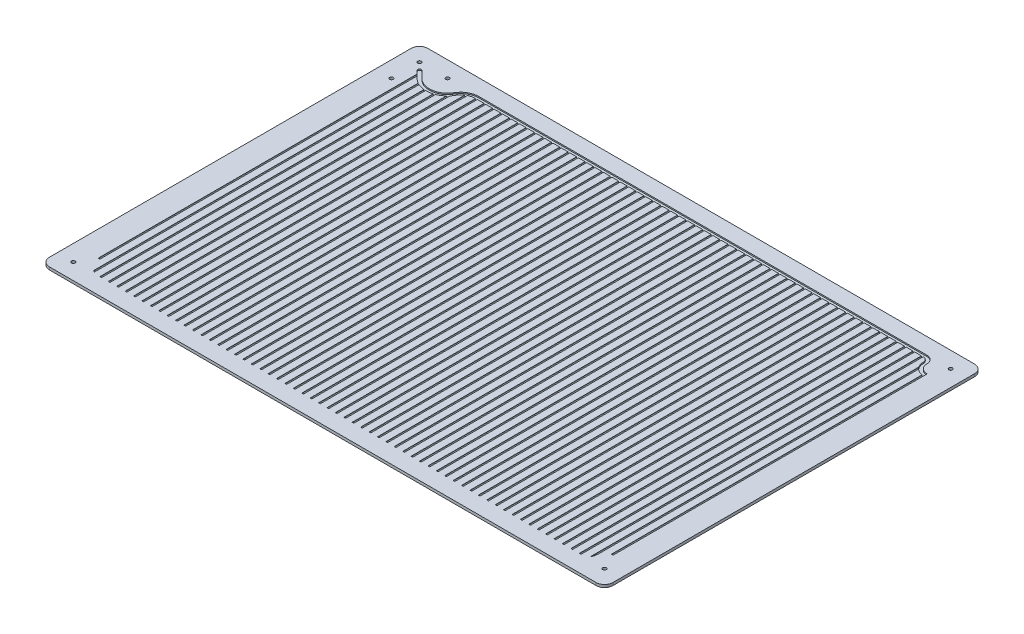
SolidWorks part; units mm, degrees
material "Alumina"
ref_plane "Front Plane" through (0, 0, 0) normal (0, 0, 1) x (1, 0, 0)
ref_plane "Top Plane" through (0, 0, 0) normal (0, 1, 0) x (1, 0, 0)
ref_plane "Right Plane" through (0, 0, 0) normal (1, 0, 0) x (0, 0, -1)
sketch "Sketch1" plane through (0, 0, 0) normal (0, 1, 0) x (1, 0, 0)
  line L1 (-300, -225) -> (300, -225)
  line L2 (-300, -225) -> (-300, 225) construction
  line L3 (-300, 225) -> (300, 225)
  line L4 (300, -225) -> (300, 225)
  line L5 (-300, -225) -> (300, 225) construction
  line L6 (-300, 225) -> (300, -225) construction
  line L7 (-370, -225) -> (-300, -225)
  line L8 (-370, -225) -> (-370, 225)
  line L9 (-370, 225) -> (-300, 225)
  line L10 (-300, -225) -> (-300, 225)
  line L11 (-370, -225) -> (-300, 225) construction
  line L12 (-370, 225) -> (-300, -225) construction
  point P0 (0, 0)
  point P6 (-335, 0)
  dimension "D1" = 450
  dimension "D2" = 600
  dimension "D3" = 70
extrude "Boss-Extrude1" add sketch "Sketch1" along normal blind 3.2 contours L7 L10 L9 L8 | L10 L1 L4 L3 region at (0, 0, 0) region at (-335, 0, 0)
sketch "Sketch2" plane through (0, 3.2, 0) normal (0, 1, 0) x (1, 0, 0)
  line L0 (-300, -225) -> (300, -225) construction
  line L1 (300, -225) -> (300, 225) construction
  line L2 (-300, 225) -> (300, 225) construction
  line L3 (-370, 225) -> (-300, 225) construction
  line L4 (-370, -225) -> (-370, 225) construction
  line L6 (-300, -225) -> (300, -225) construction
  line L7 (300, -225) -> (300, 225) construction
  line L8 (-300, 225) -> (300, 225) construction
  line L9 (-370, 225) -> (-300, 225) construction
  line L10 (-370, -225) -> (-370, 225) construction
  line L12 (-370, 225) -> (-350.8076, 205.8076) construction
  line L13 (-350.8076, 205.8076) -> (280.8076, 205.8076) construction
  line L14 (-350.8076, 205.8076) -> (-350.8076, -205.8076) construction
  line L15 (-350.8076, -205.8076) -> (280.8076, -205.8076) construction
  line L16 (280.8076, 205.8076) -> (280.8076, -205.8076) construction
  line L17 (280.8076, 205.8076) -> (300, 225) construction
  line L18 (280.8076, -205.8076) -> (300, -225) construction
  line L19 (-340.8076, 215.8076) -> (35014.5314, 35571.1467) construction
  line L20 (-35, 205.8076) -> (-35, -49794.1924) construction
  line L21 (0, 0) -> (50000, 0) construction
  line L22 (-331.6152, 186.6152) -> (35023.723, -35168.7247) construction
  line L23 (-270, 225) -> (-370, 125) construction
  circle A0 centre (-350.8076, 205.8076) radius 3 construction
  arc A1 (-370, 215) -> (-360, 225) centre (-360, 215) cw construction
  arc A2 (-341.6152, 186.6152) -> (-331.6152, 196.6152) centre (-341.6152, 196.6152) ccw construction
  arc A3 (271.6152, 186.6152) -> (261.6152, 196.6152) centre (271.6152, 196.6152) cw construction
  arc A4 (271.6152, -186.6152) -> (261.6152, -196.6152) centre (271.6152, -196.6152) ccw construction
  arc A5 (-341.6152, 186.6152) -> (-350.8076, 177.4228) centre (-341.6152, 177.4228) ccw construction
  arc A6 (-331.6152, 196.6152) -> (-322.4228, 205.8076) centre (-322.4228, 196.6152) cw construction
  arc A7 (271.6152, 186.6152) -> (280.8076, 177.4228) centre (271.6152, 177.4228) cw construction
  arc A8 (261.6152, 196.6152) -> (252.4228, 205.8076) centre (252.4228, 196.6152) ccw construction
  arc A9 (261.6152, -196.6152) -> (252.4228, -205.8076) centre (252.4228, -196.6152) cw construction
  arc A10 (271.6152, -186.6152) -> (280.8076, -177.4228) centre (271.6152, -177.4228) ccw construction
  circle A11 centre (-350.8076, 172.4767) radius 3 construction
  circle A13 centre (-317.4767, 205.8076) radius 3 construction
  arc A15 (-331.6152, -196.6152) -> (-322.4228, -205.8076) centre (-322.4228, -196.6152) ccw construction
  arc A16 (-341.6152, -186.6152) -> (-331.6152, -196.6152) centre (-341.6152, -196.6152) cw construction
  arc A17 (-341.6152, -186.6152) -> (-350.8076, -177.4228) centre (-341.6152, -177.4228) cw construction
  point P10 (-352.9289, 207.9289)
  point P16 (-367.0711, 222.0711)
  point P27 (-35, 205.8076)
  point P39 (-334.5442, 189.5442)
  point P53 (-350.8076, 175.4767)
  point P56 (-350.8076, 202.8076)
  dimension "D2" = 6
  dimension "D3" = 10
  dimension "D1" = 45
  dimension "D4" = 20
  dimension "D5" = 45
  dimension "D6" = 100
  dimension "D7" = 20
  dimension "D8" = 27.3309
sketch "Sketch6" plane through (0, 3.2, 0) normal (0, 1, 0) x (1, 0, 0)
  line L0 (280.8076, 177.4228) -> (280.8076, -177.4228) construction
  line L1 (-280, 205.8076) -> (252.4228, 205.8076) construction
  line L2 (-350.8076, 205.8076) -> (280.8076, 205.8076) construction
  line L5 (-350.8076, -205.8076) -> (280.8076, -205.8076) construction
  line L6 (-280, -205.8076) -> (252.4228, -205.8076) construction
  line L7 (-141752.968, 141607.9749) -> (176445.0758, -176590.0843) construction
  line L8 (-341.0607, 198.8891) -> (-332.7279, 190.5564)
  line L9 (-343.8891, 196.0607) -> (-341.0607, 198.8891) construction
  line L10 (-350.8076, 172.4767) -> (-317.4767, 205.8076) construction
  line L11 (-350.8076, 205.8076) -> (-334.1421, 189.1421) construction
  line L12 (-343.8891, 196.0607) -> (-335.5564, 187.7279)
  line L13 (-283.4499, 201.8076) -> (-67.3575, 201.8076) construction
  line L14 (-280, 205.8076) -> (-280, 201.8076)
  line L16 (-280, 224.1399) -> (-280, -49775.8601) construction
  line L17 (-300, -225) -> (-300, 225) construction
  line L18 (-300, -225) -> (-300, 225) construction
  arc A0 (271.6152, -186.6152) -> (280.8076, -177.4228) centre (271.6152, -177.4228) ccw construction
  arc A1 (271.6152, -186.6152) -> (261.6152, -196.6152) centre (271.6152, -196.6152) ccw construction
  arc A2 (252.4228, -205.8076) -> (261.6152, -196.6152) centre (252.4228, -196.6152) ccw construction
  arc A3 (280.8076, 177.4228) -> (271.6152, 186.6152) centre (271.6152, 177.4228) ccw construction
  arc A4 (261.6152, 196.6152) -> (271.6152, 186.6152) centre (271.6152, 196.6152) ccw construction
  arc A5 (261.6152, 196.6152) -> (252.4228, 205.8076) centre (252.4228, 196.6152) ccw construction
  arc A6 (271.6152, -186.6152) -> (280.8076, -177.4228) centre (271.6152, -177.4228) ccw construction
  arc A7 (271.6152, -186.6152) -> (261.6152, -196.6152) centre (271.6152, -196.6152) ccw construction
  arc A8 (252.4228, -205.8076) -> (261.6152, -196.6152) centre (252.4228, -196.6152) ccw construction
  arc A9 (280.8076, 177.4228) -> (271.6152, 186.6152) centre (271.6152, 177.4228) ccw construction
  arc A10 (261.6152, 196.6152) -> (271.6152, 186.6152) centre (271.6152, 196.6152) ccw construction
  arc A11 (261.6152, 196.6152) -> (252.4228, 205.8076) centre (252.4228, 196.6152) ccw construction
  arc A12 (-298.8275, 194.972) -> (-332.7279, 190.5564) centre (-317.4767, 205.8076) cw
  arc A13 (-335.5564, 187.7279) -> (-295.3689, 192.9625) centre (-317.4767, 205.8076) ccw
  arc A14 (-341.0607, 198.8891) -> (-343.8891, 196.0607) centre (-342.4749, 197.4749) ccw
  arc A15 (-298.8275, 194.972) -> (-280, 205.8076) centre (-280, 184.0329) cw
  arc A16 (-295.3689, 192.9625) -> (-280, 201.8076) centre (-280, 184.0329) cw
  point P31 (-342.4749, 197.4749)
  dimension "D1" = 4
  dimension "D2" = 20
extrude "Cut-Extrude1" cut sketch "Sketch6" against normal blind 1.5
hole_wizard "Tap Drill for M5x0.8 Tap2" positions "3DSketch4" profile "Sketch10" hole size "M5x0.8" standard "ANSI Metric" end condition through all
sketch3d "3DSketch4"
  point P0 (-350.8076, 3.2, 205.8076)
  point P3 (-350.8076, 3.2, -205.8076)
  point P6 (-317.4767, 3.2, -205.8076)
  point P9 (-350.8076, 3.2, -172.4767)
  point P12 (280.8076, 3.2, -205.8076)
  point P15 (280.8076, 3.2, 205.8076)
sketch "Sketch10" plane through (-350.8076, 3.2, 205.8076) normal (1, 0, 0) x (0, 0, 1)
  line L0 (0, 0) -> (0, 3.2)
  line L1 (0, 3.2) -> (2.1, 3.2)
  line L2 (2.1, 3.2) -> (2.1, 0)
  line L5 (2.1, 0) -> (0, 0)
  line L11 (0, -6.35) -> (0, 107.95) construction
  dimension "Thru Hole Dia." = 4.2
  dimension "Thru Hole Depth" = 3.2
sketch "Sketch11" plane through (0, 0, 225) normal (0, 0, 1) x (1, 0, 0)
  line L0 (-280, 3.2) -> (-298.8275, 3.2) construction
  line L1 (-280, 3.2) -> (-298.8275, 3.2) construction
  line L3 (-280, 3.2) -> (-280, 2.7)
  line L4 (-280, 3.2) -> (-278, 3.2)
  line L5 (-141762.1638, 3.2) -> (176435.8877, 3.2) construction
  line L6 (-278, 3.2) -> (-278, 2.7)
  line L7 (-270, 3.2) -> (-270, 2.7)
  line L8 (-270, 3.2) -> (-268, 3.2)
  line L9 (-268, 3.2) -> (-268, 2.7)
  line L10 (-260, 3.2) -> (-260, 2.7)
  line L11 (-260, 3.2) -> (-258, 3.2)
  line L12 (-258, 3.2) -> (-258, 2.7)
  line L13 (-250, 3.2) -> (-250, 2.7)
  line L14 (-250, 3.2) -> (-248, 3.2)
  line L15 (-248, 3.2) -> (-248, 2.7)
  line L16 (-240, 3.2) -> (-240, 2.7)
  line L17 (-240, 3.2) -> (-238, 3.2)
  line L18 (-238, 3.2) -> (-238, 2.7)
  line L19 (-230, 3.2) -> (-230, 2.7)
  line L20 (-230, 3.2) -> (-228, 3.2)
  line L21 (-228, 3.2) -> (-228, 2.7)
  line L22 (-220, 3.2) -> (-220, 2.7)
  line L23 (-220, 3.2) -> (-218, 3.2)
  line L24 (-218, 3.2) -> (-218, 2.7)
  line L25 (-210, 3.2) -> (-210, 2.7)
  line L26 (-210, 3.2) -> (-208, 3.2)
  line L27 (-208, 3.2) -> (-208, 2.7)
  line L28 (-200, 3.2) -> (-200, 2.7)
  line L29 (-200, 3.2) -> (-198, 3.2)
  line L30 (-198, 3.2) -> (-198, 2.7)
  line L31 (-190, 3.2) -> (-190, 2.7)
  line L32 (-190, 3.2) -> (-188, 3.2)
  line L33 (-188, 3.2) -> (-188, 2.7)
  line L34 (-180, 3.2) -> (-180, 2.7)
  line L35 (-180, 3.2) -> (-178, 3.2)
  line L36 (-178, 3.2) -> (-178, 2.7)
  line L37 (-170, 3.2) -> (-170, 2.7)
  line L38 (-170, 3.2) -> (-168, 3.2)
  line L39 (-168, 3.2) -> (-168, 2.7)
  line L40 (-160, 3.2) -> (-160, 2.7)
  line L41 (-160, 3.2) -> (-158, 3.2)
  line L42 (-158, 3.2) -> (-158, 2.7)
  line L43 (-150, 3.2) -> (-150, 2.7)
  line L44 (-150, 3.2) -> (-148, 3.2)
  line L45 (-148, 3.2) -> (-148, 2.7)
  line L46 (-140, 3.2) -> (-140, 2.7)
  line L47 (-140, 3.2) -> (-138, 3.2)
  line L48 (-138, 3.2) -> (-138, 2.7)
  line L49 (-130, 3.2) -> (-130, 2.7)
  line L50 (-130, 3.2) -> (-128, 3.2)
  line L51 (-128, 3.2) -> (-128, 2.7)
  line L52 (-120, 3.2) -> (-120, 2.7)
  line L53 (-120, 3.2) -> (-118, 3.2)
  line L54 (-118, 3.2) -> (-118, 2.7)
  line L55 (-110, 3.2) -> (-110, 2.7)
  line L56 (-110, 3.2) -> (-108, 3.2)
  line L57 (-108, 3.2) -> (-108, 2.7)
  line L58 (-100, 3.2) -> (-100, 2.7)
  line L59 (-100, 3.2) -> (-98, 3.2)
  line L60 (-98, 3.2) -> (-98, 2.7)
  line L61 (-90, 3.2) -> (-90, 2.7)
  line L62 (-90, 3.2) -> (-88, 3.2)
  line L63 (-88, 3.2) -> (-88, 2.7)
  line L64 (-80, 3.2) -> (-80, 2.7)
  line L65 (-80, 3.2) -> (-78, 3.2)
  line L66 (-78, 3.2) -> (-78, 2.7)
  line L67 (-70, 3.2) -> (-70, 2.7)
  line L68 (-70, 3.2) -> (-68, 3.2)
  line L69 (-68, 3.2) -> (-68, 2.7)
  line L70 (-60, 3.2) -> (-60, 2.7)
  line L71 (-60, 3.2) -> (-58, 3.2)
  line L72 (-58, 3.2) -> (-58, 2.7)
  line L73 (-50, 3.2) -> (-50, 2.7)
  line L74 (-50, 3.2) -> (-48, 3.2)
  line L75 (-48, 3.2) -> (-48, 2.7)
  line L76 (-40, 3.2) -> (-40, 2.7)
  line L77 (-40, 3.2) -> (-38, 3.2)
  line L78 (-38, 3.2) -> (-38, 2.7)
  line L79 (-30, 3.2) -> (-30, 2.7)
  line L80 (-30, 3.2) -> (-28, 3.2)
  line L81 (-28, 3.2) -> (-28, 2.7)
  line L82 (-20, 3.2) -> (-20, 2.7)
  line L83 (-20, 3.2) -> (-18, 3.2)
  line L84 (-18, 3.2) -> (-18, 2.7)
  line L85 (-10, 3.2) -> (-10, 2.7)
  line L86 (-10, 3.2) -> (-8, 3.2)
  line L87 (-8, 3.2) -> (-8, 2.7)
  line L88 (0, 3.2) -> (0, 2.7)
  line L89 (0, 3.2) -> (2, 3.2)
  line L90 (2, 3.2) -> (2, 2.7)
  line L91 (10, 3.2) -> (10, 2.7)
  line L92 (10, 3.2) -> (12, 3.2)
  line L93 (12, 3.2) -> (12, 2.7)
  line L94 (20, 3.2) -> (20, 2.7)
  line L95 (20, 3.2) -> (22, 3.2)
  line L96 (22, 3.2) -> (22, 2.7)
  line L97 (30, 3.2) -> (30, 2.7)
  line L98 (30, 3.2) -> (32, 3.2)
  line L99 (32, 3.2) -> (32, 2.7)
  line L100 (40, 3.2) -> (40, 2.7)
  line L101 (40, 3.2) -> (42, 3.2)
  line L102 (42, 3.2) -> (42, 2.7)
  line L103 (50, 3.2) -> (50, 2.7)
  line L104 (50, 3.2) -> (52, 3.2)
  line L105 (52, 3.2) -> (52, 2.7)
  line L106 (60, 3.2) -> (60, 2.7)
  line L107 (60, 3.2) -> (62, 3.2)
  line L108 (62, 3.2) -> (62, 2.7)
  line L109 (70, 3.2) -> (70, 2.7)
  line L110 (70, 3.2) -> (72, 3.2)
  line L111 (72, 3.2) -> (72, 2.7)
  line L112 (80, 3.2) -> (80, 2.7)
  line L113 (80, 3.2) -> (82, 3.2)
  line L114 (82, 3.2) -> (82, 2.7)
  line L115 (90, 3.2) -> (90, 2.7)
  line L116 (90, 3.2) -> (92, 3.2)
  line L117 (92, 3.2) -> (92, 2.7)
  line L118 (100, 3.2) -> (100, 2.7)
  line L119 (100, 3.2) -> (102, 3.2)
  line L120 (102, 3.2) -> (102, 2.7)
  line L121 (110, 3.2) -> (110, 2.7)
  line L122 (110, 3.2) -> (112, 3.2)
  line L123 (112, 3.2) -> (112, 2.7)
  line L124 (120, 3.2) -> (120, 2.7)
  line L125 (120, 3.2) -> (122, 3.2)
  line L126 (122, 3.2) -> (122, 2.7)
  line L127 (130, 3.2) -> (130, 2.7)
  line L128 (130, 3.2) -> (132, 3.2)
  line L129 (132, 3.2) -> (132, 2.7)
  line L130 (140, 3.2) -> (140, 2.7)
  line L131 (140, 3.2) -> (142, 3.2)
  line L132 (142, 3.2) -> (142, 2.7)
  line L133 (150, 3.2) -> (150, 2.7)
  line L134 (150, 3.2) -> (152, 3.2)
  line L135 (152, 3.2) -> (152, 2.7)
  line L136 (160, 3.2) -> (160, 2.7)
  line L137 (160, 3.2) -> (162, 3.2)
  line L138 (162, 3.2) -> (162, 2.7)
  line L139 (170, 3.2) -> (170, 2.7)
  line L140 (170, 3.2) -> (172, 3.2)
  line L141 (172, 3.2) -> (172, 2.7)
  line L142 (180, 3.2) -> (180, 2.7)
  line L143 (180, 3.2) -> (182, 3.2)
  line L144 (182, 3.2) -> (182, 2.7)
  line L145 (190, 3.2) -> (190, 2.7)
  line L146 (190, 3.2) -> (192, 3.2)
  line L147 (192, 3.2) -> (192, 2.7)
  line L148 (200, 3.2) -> (200, 2.7)
  line L149 (200, 3.2) -> (202, 3.2)
  line L150 (202, 3.2) -> (202, 2.7)
  line L151 (210, 3.2) -> (210, 2.7)
  line L152 (210, 3.2) -> (212, 3.2)
  line L153 (212, 3.2) -> (212, 2.7)
  line L154 (220, 3.2) -> (220, 2.7)
  line L155 (220, 3.2) -> (222, 3.2)
  line L156 (222, 3.2) -> (222, 2.7)
  line L157 (230, 3.2) -> (230, 2.7)
  line L158 (230, 3.2) -> (232, 3.2)
  line L159 (232, 3.2) -> (232, 2.7)
  line L160 (240, 3.2) -> (240, 2.7)
  line L161 (240, 3.2) -> (242, 3.2)
  line L162 (242, 3.2) -> (242, 2.7)
  line L163 (250, 3.2) -> (250, 2.7)
  line L164 (250, 3.2) -> (252, 3.2)
  line L165 (252, 3.2) -> (252, 2.7)
  line L166 (260, 3.2) -> (260, 2.7)
  line L167 (260, 3.2) -> (262, 3.2)
  line L168 (262, 3.2) -> (262, 2.7)
  line L169 (270, 3.2) -> (270, 2.7)
  line L170 (270, 3.2) -> (272, 3.2)
  line L171 (272, 3.2) -> (272, 2.7)
  line L172 (-280, 3.2) -> (-270, 3.2) construction
  line L173 (-300, 3.2) -> (300, 3.2) construction
  line L174 (-290, 3.2) -> (-290, 2.7)
  line L175 (-288, 3.2) -> (-288, 2.7)
  line L176 (-290, 3.2) -> (-288, 3.2)
  line L177 (-300, 3.2) -> (-300, 2.7)
  line L178 (-298, 3.2) -> (-298, 2.7)
  line L179 (-300, 3.2) -> (-298, 3.2)
  line L180 (-310, 3.2) -> (-310, 2.7)
  line L181 (-308, 3.2) -> (-308, 2.7)
  line L182 (-310, 3.2) -> (-308, 3.2)
  line L183 (-320, 3.2) -> (-320, 2.7)
  line L184 (-318, 3.2) -> (-318, 2.7)
  line L185 (-320, 3.2) -> (-318, 3.2)
  line L186 (-330, 3.2) -> (-330, 2.7)
  line L187 (-328, 3.2) -> (-328, 2.7)
  line L188 (-330, 3.2) -> (-328, 3.2)
  line L189 (-340, 3.2) -> (-340, 2.7)
  line L190 (-338, 3.2) -> (-338, 2.7)
  line L191 (-340, 3.2) -> (-338, 3.2)
  line L192 (-280, 2.7) -> (-290, 2.7) construction
  arc A0 (-280, 2.7) -> (-278, 2.7) centre (-279, 2.7) ccw
  arc A1 (-270, 2.7) -> (-268, 2.7) centre (-269, 2.7) ccw
  arc A2 (-260, 2.7) -> (-258, 2.7) centre (-259, 2.7) ccw
  arc A3 (-250, 2.7) -> (-248, 2.7) centre (-249, 2.7) ccw
  arc A4 (-240, 2.7) -> (-238, 2.7) centre (-239, 2.7) ccw
  arc A5 (-230, 2.7) -> (-228, 2.7) centre (-229, 2.7) ccw
  arc A6 (-220, 2.7) -> (-218, 2.7) centre (-219, 2.7) ccw
  arc A7 (-210, 2.7) -> (-208, 2.7) centre (-209, 2.7) ccw
  arc A8 (-200, 2.7) -> (-198, 2.7) centre (-199, 2.7) ccw
  arc A9 (-190, 2.7) -> (-188, 2.7) centre (-189, 2.7) ccw
  arc A10 (-180, 2.7) -> (-178, 2.7) centre (-179, 2.7) ccw
  arc A11 (-170, 2.7) -> (-168, 2.7) centre (-169, 2.7) ccw
  arc A12 (-160, 2.7) -> (-158, 2.7) centre (-159, 2.7) ccw
  arc A13 (-150, 2.7) -> (-148, 2.7) centre (-149, 2.7) ccw
  arc A14 (-140, 2.7) -> (-138, 2.7) centre (-139, 2.7) ccw
  arc A15 (-130, 2.7) -> (-128, 2.7) centre (-129, 2.7) ccw
  arc A16 (-120, 2.7) -> (-118, 2.7) centre (-119, 2.7) ccw
  arc A17 (-110, 2.7) -> (-108, 2.7) centre (-109, 2.7) ccw
  arc A18 (-100, 2.7) -> (-98, 2.7) centre (-99, 2.7) ccw
  arc A19 (-90, 2.7) -> (-88, 2.7) centre (-89, 2.7) ccw
  arc A20 (-80, 2.7) -> (-78, 2.7) centre (-79, 2.7) ccw
  arc A21 (-70, 2.7) -> (-68, 2.7) centre (-69, 2.7) ccw
  arc A22 (-60, 2.7) -> (-58, 2.7) centre (-59, 2.7) ccw
  arc A23 (-50, 2.7) -> (-48, 2.7) centre (-49, 2.7) ccw
  arc A24 (-40, 2.7) -> (-38, 2.7) centre (-39, 2.7) ccw
  arc A25 (-30, 2.7) -> (-28, 2.7) centre (-29, 2.7) ccw
  arc A26 (-20, 2.7) -> (-18, 2.7) centre (-19, 2.7) ccw
  arc A27 (-10, 2.7) -> (-8, 2.7) centre (-9, 2.7) ccw
  arc A28 (0, 2.7) -> (2, 2.7) centre (1, 2.7) ccw
  arc A29 (10, 2.7) -> (12, 2.7) centre (11, 2.7) ccw
  arc A30 (20, 2.7) -> (22, 2.7) centre (21, 2.7) ccw
  arc A31 (30, 2.7) -> (32, 2.7) centre (31, 2.7) ccw
  arc A32 (40, 2.7) -> (42, 2.7) centre (41, 2.7) ccw
  arc A33 (50, 2.7) -> (52, 2.7) centre (51, 2.7) ccw
  arc A34 (60, 2.7) -> (62, 2.7) centre (61, 2.7) ccw
  arc A35 (70, 2.7) -> (72, 2.7) centre (71, 2.7) ccw
  arc A36 (80, 2.7) -> (82, 2.7) centre (81, 2.7) ccw
  arc A37 (90, 2.7) -> (92, 2.7) centre (91, 2.7) ccw
  arc A38 (100, 2.7) -> (102, 2.7) centre (101, 2.7) ccw
  arc A39 (110, 2.7) -> (112, 2.7) centre (111, 2.7) ccw
  arc A40 (120, 2.7) -> (122, 2.7) centre (121, 2.7) ccw
  arc A41 (130, 2.7) -> (132, 2.7) centre (131, 2.7) ccw
  arc A42 (140, 2.7) -> (142, 2.7) centre (141, 2.7) ccw
  arc A43 (150, 2.7) -> (152, 2.7) centre (151, 2.7) ccw
  arc A44 (160, 2.7) -> (162, 2.7) centre (161, 2.7) ccw
  arc A45 (170, 2.7) -> (172, 2.7) centre (171, 2.7) ccw
  arc A46 (180, 2.7) -> (182, 2.7) centre (181, 2.7) ccw
  arc A47 (190, 2.7) -> (192, 2.7) centre (191, 2.7) ccw
  arc A48 (200, 2.7) -> (202, 2.7) centre (201, 2.7) ccw
  arc A49 (210, 2.7) -> (212, 2.7) centre (211, 2.7) ccw
  arc A50 (220, 2.7) -> (222, 2.7) centre (221, 2.7) ccw
  arc A51 (230, 2.7) -> (232, 2.7) centre (231, 2.7) ccw
  arc A52 (240, 2.7) -> (242, 2.7) centre (241, 2.7) ccw
  arc A53 (250, 2.7) -> (252, 2.7) centre (251, 2.7) ccw
  arc A54 (260, 2.7) -> (262, 2.7) centre (261, 2.7) ccw
  arc A55 (270, 2.7) -> (272, 2.7) centre (271, 2.7) ccw
  arc A56 (-290, 2.7) -> (-288, 2.7) centre (-289, 2.7) ccw
  arc A57 (-300, 2.7) -> (-298, 2.7) centre (-299, 2.7) ccw
  arc A58 (-310, 2.7) -> (-308, 2.7) centre (-309, 2.7) ccw
  arc A59 (-320, 2.7) -> (-318, 2.7) centre (-319, 2.7) ccw
  arc A60 (-330, 2.7) -> (-328, 2.7) centre (-329, 2.7) ccw
  arc A61 (-340, 2.7) -> (-338, 2.7) centre (-339, 2.7) ccw
  point P0 (-300, 3.2)
  dimension "D2" = 1
  dimension "D1" = 0.5
  dimension "D4" = 10
  dimension "D6" = 10
  dimension "D3" = 56
  dimension "D5" = 7
extrude "Cut-Extrude2" cut sketch "Sketch11" against normal offset from surface (410 mm away) 20 from offset 20 up to face at (-35, 1.6, -225) offset against normal yes
sketch "Sketch12" plane through (0, 3.2, 0) normal (0, 1, 0) x (1, 0, 0)
  line L0 (-280, 205.8076) -> (-315.3767, 205.8076)
  line L1 (-350.8076, 205.8076) -> (280.8076, 205.8076) construction
  line L2 (-350.8076, 205.8076) -> (-350.8076, -205.8076) construction
  line L3 (-350.8076, 202.8076) -> (-350.8076, 177.4228)
  line L4 (-350.8076, -177.4228) -> (-350.8076, -203.7076)
  line L5 (-332.7279, 190.5564) -> (-339, 196.8284)
  line L6 (-339, 196.8284) -> (-341.0607, 198.8891)
  line L7 (-343.8891, 196.0607) -> (-339, 191.1716)
  line L8 (-339, 191.1716) -> (-335.5564, 187.7279)
  line L9 (-280, 201.8076) -> (-280, 205.8076)
  line L10 (-332.7279, 190.5564) -> (-339, 196.8284)
  line L11 (-339, 196.8284) -> (-341.0607, 198.8891)
  line L12 (-343.8891, 196.0607) -> (-340, 192.1716)
  line L15 (-350.8076, -205.8076) -> (280.8076, -205.8076) construction
  line L16 (-348.7076, -205.8076) -> (-322.4228, -205.8076)
  line L17 (-35, -225) -> (-35, 49775) construction
  line L19 (-35, 200205.8076) -> (-35, -249794.1924) construction
  line L20 (0, 0) -> (-49761.8351, 0) construction
  line L22 (-200000, 0) -> (250000, 0) construction
  line L23 (278.7076, -205.8076) -> (252.4228, -205.8076)
  line L24 (280.8076, -177.4228) -> (280.8076, -203.7076)
  line L25 (280.8076, 177.4228) -> (280.8076, 203.7076)
  line L26 (278.7076, 205.8076) -> (252.4228, 205.8076)
  line L27 (-319.5767, 205.8076) -> (-347.8076, 205.8076)
  line L28 (-340, 192.1716) -> (-340, 186.7465)
  line L29 (-340, 192.1716) -> (-340, -205) construction
  arc A6 (-331.6152, -196.6152) -> (-322.4228, -205.8076) centre (-322.4228, -196.6152) ccw construction
  arc A7 (-331.6152, -196.6152) -> (-341.6152, -186.6152) centre (-341.6152, -196.6152) ccw construction
  arc A8 (-350.8076, -177.4228) -> (-341.6152, -186.6152) centre (-341.6152, -177.4228) ccw construction
  arc A9 (280.8076, -203.7076) -> (278.7076, -205.8076) centre (280.8076, -205.8076) ccw
  arc A10 (280.8076, -177.4228) -> (271.6152, -186.6152) centre (271.6152, -177.4228) cw
  arc A11 (261.6152, -196.6152) -> (271.6152, -186.6152) centre (271.6152, -196.6152) cw
  arc A12 (261.6152, -196.6152) -> (252.4228, -205.8076) centre (252.4228, -196.6152) cw
  arc A13 (261.6152, 196.6152) -> (252.4228, 205.8076) centre (252.4228, 196.6152) ccw
  arc A14 (261.6152, 196.6152) -> (271.6152, 186.6152) centre (271.6152, 196.6152) ccw
  arc A15 (-280, 205.8076) -> (-289, 203.8606) centre (-280, 184.0329) ccw
  arc A16 (-289, 203.8606) -> (-298.8275, 194.972) centre (-280, 184.0329) ccw
  arc A17 (-299, 194.6804) -> (-298.8275, 194.972) centre (-317.4767, 205.8076) ccw
  arc A18 (-309, 185.9746) -> (-299, 194.6804) centre (-317.4767, 205.8076) ccw
  arc A19 (-319, 184.2929) -> (-309, 185.9746) centre (-317.4767, 205.8076) ccw
  arc A20 (-329, 187.5754) -> (-319, 184.2929) centre (-317.4767, 205.8076) ccw
  arc A21 (-332.7279, 190.5564) -> (-329, 187.5754) centre (-317.4767, 205.8076) ccw
  arc A22 (-341.0607, 198.8891) -> (-343.8891, 196.0607) centre (-342.4749, 197.4749) ccw
  arc A23 (-335.5564, 187.7279) -> (-329, 182.983) centre (-317.4767, 205.8076) ccw
  arc A24 (-329, 182.983) -> (-319, 180.2845) centre (-317.4767, 205.8076) ccw
  arc A25 (-319, 180.2845) -> (-309, 181.6851) centre (-317.4767, 205.8076) ccw
  arc A26 (-309, 181.6851) -> (-299, 188.1338) centre (-317.4767, 205.8076) ccw
  arc A27 (-299, 188.1338) -> (-295.3689, 192.9625) centre (-317.4767, 205.8076) ccw
  arc A28 (-289, 199.3607) -> (-295.3689, 192.9625) centre (-280, 184.0329) ccw
  arc A29 (-280, 201.8076) -> (-289, 199.3607) centre (-280, 184.0329) ccw
  arc A30 (-280, 205.8076) -> (-289, 203.8606) centre (-280, 184.0329) ccw
  arc A31 (-289, 203.8606) -> (-298.8275, 194.972) centre (-280, 184.0329) ccw
  arc A32 (-299, 194.6804) -> (-298.8275, 194.972) centre (-317.4767, 205.8076) ccw
  arc A33 (-309, 185.9746) -> (-299, 194.6804) centre (-317.4767, 205.8076) ccw
  arc A34 (-319, 184.2929) -> (-309, 185.9746) centre (-317.4767, 205.8076) ccw
  arc A35 (-329, 187.5754) -> (-319, 184.2929) centre (-317.4767, 205.8076) ccw
  arc A36 (-332.7279, 190.5564) -> (-329, 187.5754) centre (-317.4767, 205.8076) ccw
  arc A37 (-341.0607, 198.8891) -> (-343.8891, 196.0607) centre (-342.4749, 197.4749) ccw
  arc A45 (-331.6152, -196.6152) -> (-322.4228, -205.8076) centre (-322.4228, -196.6152) ccw
  arc A46 (-331.6152, -196.6152) -> (-341.6152, -186.6152) centre (-341.6152, -196.6152) ccw
  arc A47 (-350.8076, -177.4228) -> (-341.6152, -186.6152) centre (-341.6152, -177.4228) ccw
  arc A48 (-347.8076, 205.8076) -> (-350.8076, 202.8076) centre (-350.8076, 205.8076) cw
  circle A49 centre (-350.8076, 205.8076) radius 3 construction
  arc A51 (-341.6152, 186.6152) -> (-331.6152, 196.6152) centre (-341.6152, 196.6152) ccw construction
  arc A52 (-341.6152, 186.6152) -> (-350.8076, 177.4228) centre (-341.6152, 177.4228) ccw construction
  circle A53 centre (-350.8076, -205.8076) radius 2.1 construction
  arc A54 (-341.6152, 186.6152) -> (-340, 186.7465) centre (-341.6152, 196.6152) ccw
  arc A55 (-341.6152, 186.6152) -> (-350.8076, 177.4228) centre (-341.6152, 177.4228) ccw
  arc A56 (-350.8076, -203.7076) -> (-348.7076, -205.8076) centre (-350.8076, -205.8076) cw
  arc A57 (280.8076, 177.4228) -> (271.6152, 186.6152) centre (271.6152, 177.4228) ccw
  arc A58 (280.8076, 203.7076) -> (278.7076, 205.8076) centre (280.8076, 205.8076) cw
  arc A59 (-319.5767, 205.8076) -> (-315.3767, 205.8076) centre (-317.4767, 205.8076) ccw
  arc A60 (-318, 203.7739) -> (-319.4152, 205) centre (-317.4767, 205.8076) ccw construction
  dimension "D1" = 0
extrude "Boss-Extrude2" add sketch "Sketch12" against normal up to surface (1.5 mm away) up to face at (-313.8725, 1.7, -192.2606)
sketch "Sketch13" plane through (-280, 0, 0) normal (-1, 0, 0) x (0, 0, 1)
  line L0 (-205, 3.2) -> (-205.8076, 3.2) construction
  line L1 (-205.8076, 1.7) -> (-201.8076, 1.7)
  line L2 (-205.8076, 1.7) -> (-205.8076, 3.2)
  line L3 (-205.8076, 3.2) -> (-201.8076, 3.2)
  line L4 (-201.8076, 1.7) -> (-201.8076, 3.2)
  line L5 (-201.8076, 1.7) -> (-201.8076, 2.7) construction
extrude "Cut-Extrude3" cut sketch "Sketch13" against normal up to surface (532 mm away) up to face at (252, 2.95, 0)
sketch "Sketch14" plane through (0, 3.2, 0) normal (0, 1, 0) x (1, 0, 0)
  line L0 (252.4228, 205.8076) -> (252, 205.8076)
  line L1 (252, 205.8076) -> (252, 201.8076)
  line L2 (252, 205.8076) -> (252, -205) construction
  line L3 (252, 205.8076) -> (252, 201.8076) construction
  line L4 (251, 201.8076) -> (241, 201.8076) construction
  line L6 (272, 186.6072) -> (272, 182.6182)
  line L7 (272, 186.6072) -> (272, -186.6072) construction
  arc A0 (280.8076, 177.4228) -> (271.6152, 186.6152) centre (271.6152, 177.4228) ccw construction
  arc A1 (261.6152, 196.6152) -> (271.6152, 186.6152) centre (271.6152, 196.6152) ccw construction
  arc A2 (261.6152, 196.6152) -> (252.4228, 205.8076) centre (252.4228, 196.6152) ccw construction
  arc A3 (272, 186.6072) -> (271.6152, 186.6152) centre (271.6152, 177.4228) ccw
  arc A4 (261.6152, 196.6152) -> (271.6152, 186.6152) centre (271.6152, 196.6152) ccw
  arc A5 (261.6152, 196.6152) -> (252.4228, 205.8076) centre (252.4228, 196.6152) ccw
  arc A6 (252, 201.8076) -> (257.6324, 196.6152) centre (252.4228, 196.6152) cw
  arc A7 (257.6324, 196.6152) -> (271.6152, 182.6324) centre (271.6152, 196.6152) ccw
  arc A8 (271.6152, 182.6324) -> (272, 182.6182) centre (271.6152, 177.4228) cw
extrude "Cut-Extrude4" cut sketch "Sketch14" against normal up to surface (1.5 mm away) up to face at (-66.3645, 1.7, -199.8894)
fillet "Fillet1" radius 10 4 edges at (-370, 1.6, -225) (300, 1.6, -225) (300, 1.6, 225) (-370, 1.6, 225)
sketch "Sketch15" plane through (0, 0, 0) normal (0, -1, 0) x (1, 0, 0)
  line L0 (-35, 225) -> (-35, -225) construction
  line L1 (-360, 225) -> (290, 225) construction
  line L2 (-360, -225) -> (290, -225) construction
  line L3 (-370, 215) -> (-370, -215) construction
  line L4 (-340, -195) -> (270, -195) construction
  line L5 (-340, -195) -> (-340, 195) construction
  line L6 (-340, 195) -> (270, 195) construction
  line L7 (270, -195) -> (270, 195) construction
  line L8 (-340, -195) -> (270, 195) construction
  line L9 (-340, 195) -> (270, -195) construction
  line L11 (-340, 195) -> (-222.6923, 195)
  line L12 (-340, 195) -> (-340, 120)
  line L13 (-340, 120) -> (-222.6923, 120)
  line L14 (-222.6923, 195) -> (-222.6923, 120)
  line L15 (-340, -195) -> (-222.6923, -195)
  line L16 (-340, -195) -> (-340, -120)
  line L17 (-340, -120) -> (-222.6923, -120)
  line L18 (-222.6923, -195) -> (-222.6923, -120)
  line L19 (270, 195) -> (152.6923, 195)
  line L20 (270, 195) -> (270, 120)
  line L21 (270, 120) -> (152.6923, 120)
  line L22 (152.6923, 195) -> (152.6923, 120)
  line L23 (270, -195) -> (152.6923, -195)
  line L24 (270, -195) -> (270, -120)
  line L25 (270, -120) -> (152.6923, -120)
  line L26 (152.6923, -195) -> (152.6923, -120)
  point P6 (-35, 0)
  dimension "D1" = 30
  dimension "D2" = 30
  dimension "D3" = 75
extrude "Boss-Extrude3" add sketch "Sketch15" along normal blind 10
sketch "Sketch16" plane through (0, 0, 195) normal (0, 0, 1) x (1, 0, 0)
  line L0 (-340, 0) -> (-340, -10) construction
  line L1 (-340, -10) -> (-332.5, -10) construction
  line L2 (-222.6923, -10) -> (-340, -10) construction
  line L3 (-332.5, -10) -> (-322.5, 0)
  line L4 (-222.6923, 0) -> (-340, 0) construction
  line L5 (-322.5, 0) -> (-340, 0) construction
  line L6 (-332.5, -10) -> (-322.5, -10)
  line L7 (-322.5, -10) -> (-322.5, 0)
  line L8 (-300, -10) -> (-300, 0)
  line L9 (-310, -10) -> (-300, 0)
  line L10 (-310, -10) -> (-300, -10)
  line L11 (-277.5, -10) -> (-277.5, 0)
  line L12 (-287.5, -10) -> (-277.5, 0)
  line L13 (-287.5, -10) -> (-277.5, -10)
  line L14 (-255, -10) -> (-255, 0)
  line L15 (-265, -10) -> (-255, 0)
  line L16 (-265, -10) -> (-255, -10)
  line L17 (-232.5, -10) -> (-232.5, 0)
  line L18 (-242.5, -10) -> (-232.5, 0)
  line L19 (-242.5, -10) -> (-232.5, -10)
  line L20 (-322.5, -10) -> (-300, -10) construction
  dimension "D1" = 45
  dimension "D2" = 7.5
  dimension "D4" = 22.5
  dimension "D3" = 5
extrude "Cut-Extrude5" cut sketch "Sketch16" against normal up to surface (75 mm away) up to face at (-281.3462, -5, 120)
sketch "Sketch17" plane through (-340, 0, 0) normal (-1, 0, 0) x (0, 0, 1)
  line L10 (-127.5, 0) -> (-127.5, -10)
  line L11 (-120, 0) -> (-195, 0) construction
  line L12 (-127.5, -10) -> (-137.5, -10)
  line L13 (-137.5, -10) -> (-127.5, 0)
  line L14 (-120, -10) -> (-195, -10) construction
  line L15 (-120, -10) -> (-120, 0) construction
  line L16 (-162.5, -10) -> (-152.5, 0)
  line L17 (-152.5, -10) -> (-162.5, -10)
  line L18 (-152.5, 0) -> (-152.5, -10)
  line L19 (-187.5, -10) -> (-177.5, 0)
  line L20 (-177.5, -10) -> (-187.5, -10)
  line L21 (-177.5, 0) -> (-177.5, -10)
  line L22 (-137.5, -10) -> (-162.5, -10) construction
  dimension "D1" = 10
  dimension "D2" = 7.5
  dimension "D4" = 25
extrude "Cut-Extrude6" cut sketch "Sketch17" against normal up to surface (117.3077 mm away) up to face at (-222.6923, -5, -157.5)
sketch "Sketch18" plane through (0, 0, -195) normal (0, 0, -1) x (-1, 0, 0)
  line L0 (-160.1923, 0) -> (-160.1923, -10)
  line L1 (-152.6923, 0) -> (-270, 0) construction
  line L2 (-152.6923, -10) -> (-270, -10) construction
  line L3 (-160.1923, -10) -> (-170.1923, -10)
  line L4 (-170.1923, -10) -> (-160.1923, 0)
  line L5 (-152.6923, -10) -> (-152.6923, 0) construction
  line L6 (-182.6923, 0) -> (-182.6923, -10)
  line L7 (-182.6923, -10) -> (-192.6923, -10)
  line L8 (-192.6923, -10) -> (-182.6923, 0)
  line L9 (-205.1923, 0) -> (-205.1923, -10)
  line L10 (-205.1923, -10) -> (-215.1923, -10)
  line L11 (-215.1923, -10) -> (-205.1923, 0)
  line L12 (-227.6923, 0) -> (-227.6923, -10)
  line L13 (-227.6923, -10) -> (-237.6923, -10)
  line L14 (-237.6923, -10) -> (-227.6923, 0)
  line L15 (-250.1923, 0) -> (-250.1923, -10)
  line L16 (-250.1923, -10) -> (-260.1923, -10)
  line L17 (-260.1923, -10) -> (-250.1923, 0)
  line L18 (-160.1923, 0) -> (-182.6923, 0) construction
  dimension "D1" = 10
  dimension "D2" = 7.5
  dimension "D4" = 22.5
  dimension "D3" = 5
extrude "Cut-Extrude7" cut sketch "Sketch18" against normal up to surface (75 mm away) up to face at (211.3462, -5, -120)
sketch "Sketch19" plane through (270, 0, 0) normal (1, 0, 0) x (0, 0, -1)
  line L0 (-127.5, 0) -> (-127.5, -10)
  line L1 (-120, 0) -> (-195, 0) construction
  line L2 (-120, -10) -> (-195, -10) construction
  line L3 (-127.5, -10) -> (-137.5, -10)
  line L4 (-137.5, -10) -> (-127.5, 0)
  line L6 (-120, -10) -> (-120, 0) construction
  line L7 (-162.5, -10) -> (-152.5, 0)
  line L8 (-152.5, -10) -> (-162.5, -10)
  line L9 (-152.5, 0) -> (-152.5, -10)
  line L10 (-187.5, -10) -> (-177.5, 0)
  line L11 (-177.5, -10) -> (-187.5, -10)
  line L12 (-177.5, 0) -> (-177.5, -10)
  line L13 (-137.5, -10) -> (-162.5, -10) construction
  dimension "D1" = 10
  dimension "D4" = 25
  dimension "D2" = 7.5
extrude "Cut-Extrude8" cut sketch "Sketch19" against normal up to surface (117.3077 mm away) up to face at (152.6923, -5, 157.5)
equation "\"half_plate_thickness\"= 0.32cm'Total plate thickness: 1 cm"
equation "\"plate_length\"= 60cm'Parallel to x-axis"
equation "\"plate_width\"= 45cm'Parallel to z-axis"
equation "\"electronics_box_length\"= 10cm'Parallel to x-axis"
equation "\"wall_width\"= 2cm'Same value for wall_length"
equation "\"eds_radius\"= 1mm"
equation "\"eds_spacing\"= 10mm"
equation "\"general_tolerance\"= 0.5mm"
equation "\"eds_count\"= 57"
equation "\"plate_fillet_radius\"= 10mm"
equation "\"tooth_height\"= 1cm"
equation "\"tooth_offset\"= 0.5cm"
equation "\"tooth_patch_width\"= 7.5cm"
equation "\"D1@Sketch1\"=\"plate_width\""
equation "\"D2@Sketch1\"=\"plate_length\""
equation "\"D3@Sketch1\"=\"electronics_box_length\"-3cm"
equation "\"D1@Boss-Extrude1\"=\"half_plate_thickness\""
equation "\"D3@Sketch2\"=\"plate_fillet_radius\""
equation "\"D4@Sketch2\"=\"wall_width\""
equation "\"D6@Sketch2\"=\"electronics_box_length\""
equation "\"D7@Sketch2\"=\"wall_width\""
equation "\"D1@Sketch6\"=\"eds_radius\"*4"
equation "\"D1@Cut-Extrude1\"=\"eds_radius\"+\"general_tolerance\""
equation "\"D2@Sketch6\"=\"wall_width\""
equation "\"D1@Sketch11\"=\"general_tolerance\""
equation "\"D2@Sketch11\"=\"eds_radius\""
equation "\"D4@Sketch11\"=\"eds_spacing\""
equation "\"D6@Sketch11\"=\"eds_spacing\""
equation "\"D19@Cut-Extrude2\"=\"wall_width\""
equation "\"D1@Cut-Extrude2\"=\"wall_width\""
equation "\"D1@Fillet1\"=\"plate_fillet_radius\""
equation "\"D1@Sketch15\"=\"wall_width\"+1cm"
equation "\"D2@Sketch15\"=\"wall_width\"+1cm"
equation "\"D3@Sketch15\"=\"tooth_patch_width\""
equation "\"D1@Boss-Extrude3\"=\"tooth_height\""
equation "\"D1@Sketch17\"=\"tooth_height\""
equation "\"D1@Sketch18\"=\"tooth_height\""
equation "\"D1@Sketch19\"=\"tooth_height\""
